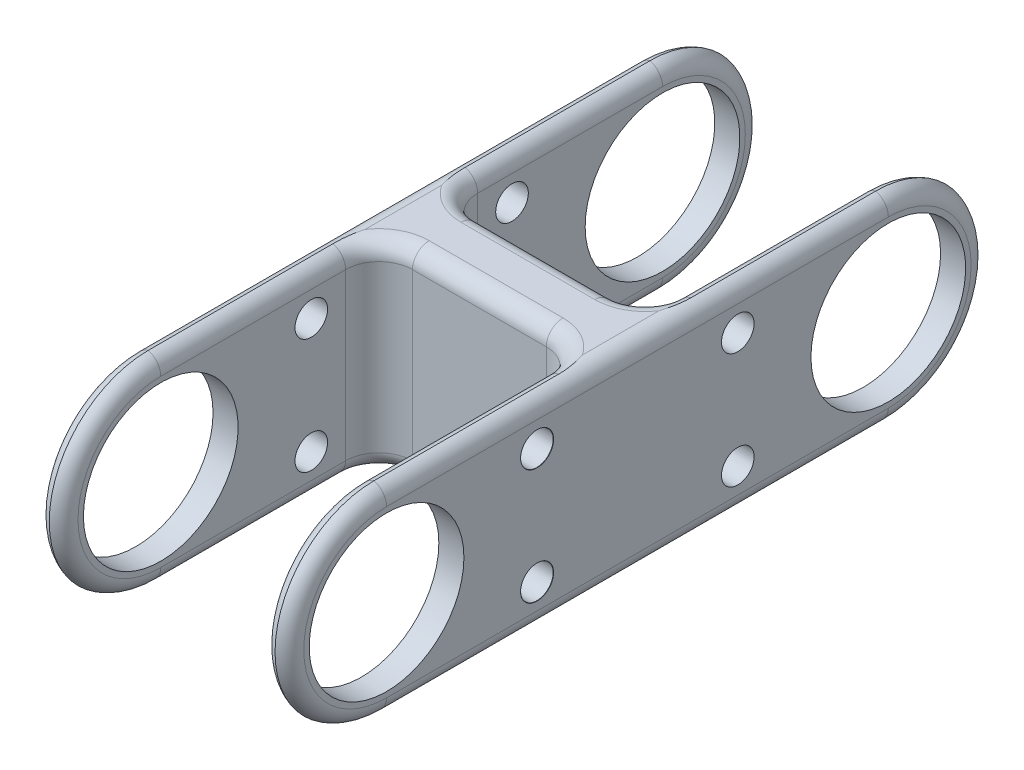
SolidWorks part; units mm, degrees
ref_plane "Front Plane" through (0, 0, 0) normal (0, 0, 1) x (1, 0, 0)
ref_plane "Top Plane" through (0, 0, 0) normal (0, 1, 0) x (1, 0, 0)
ref_plane "Right Plane" through (0, 0, 0) normal (1, 0, 0) x (0, 0, -1)
sketch "Sketch1" plane through (0, 0, 0) normal (1, 0, 0) x (0, 0, -1)
  line L0 (0, 11.9) -> (60, 11.9)
  line L1 (0, -11.9) -> (60, -11.9)
  line L2 (30, 11.9) -> (30, -11.9) construction
  circle A0 centre (0, 0) radius 9.25
  arc A1 (0, 11.9) -> (0, -11.9) centre (0, 0) ccw
  circle A2 centre (60, 0) radius 9.25
  arc A3 (60, 11.9) -> (60, -11.9) centre (60, 0) cw
  dimension "D1" = 18.5
  dimension "D2" = 23.8
  dimension "D3" = 60
extrude "Boss-Extrude1" add sketch "Sketch1" along normal blind 30
sketch "Sketch2" plane through (0, 11.9, 0) normal (0, 1, 0) x (1, 0, 0)
  line L0 (0, -11.9) -> (30, -11.9) construction
  line L1 (3, -11.9) -> (27, -11.9)
  line L2 (3, -11.9) -> (3, 26.1)
  line L3 (3, 26.1) -> (27, 26.1)
  line L4 (27, -11.9) -> (27, 26.1)
  line L5 (0, 30) -> (30, 30) construction
  line L6 (0, 60) -> (0, 0) construction
  line L7 (30, 60) -> (30, 0) construction
  line L8 (3, 33.9) -> (27, 33.9)
  line L9 (27, 71.9) -> (27, 33.9)
  line L10 (3, 71.9) -> (27, 71.9)
  line L11 (3, 71.9) -> (3, 33.9)
  dimension "D1" = 38
  dimension "D2" = 3
  dimension "D3" = 3
extrude "Cut-Extrude1" cut sketch "Sketch2" against normal through all
ref_plane "Plane1" through (0, 0, -30) normal (0, 0, 1) x (1, 0, 0)
fillet "Fillet1" radius 4 4 edges at (27, 0, -26.1) (3, 0, -26.1) (27, 0, -33.9) (3, 0, -33.9)
hole_wizard "M3.5 Clearance Hole1" positions "Sketch3" profile "Sketch4" hole size "M3.5" standard "ANSI Metric" end condition through all
sketch "Sketch3" plane through (0, 0, 0) normal (-1, 0, 0) x (0, 0, 1)
  circle A0 centre (-42, 6.9) radius 1.7024 construction
  point P0 (-42, -6.9)
  point P3 (-42, 6.9)
  point P10 (-41.9779, 15.1169)
  point P11 (-42, 6.9)
sketch "Sketch4" plane through (0, -6.9, -42) normal (0, 1, 0) x (0, 0, 1)
  line L0 (0, 0) -> (0, 30)
  line L1 (0, 30) -> (1.95, 30)
  line L2 (1.95, 30) -> (1.95, 0.025)
  line L3 (1.95, 0.025) -> (1.975, 0)
  line L5 (1.975, 0) -> (0, 0)
  line L6 (-1.95, 0.025) -> (-1.975, 0) construction
  line L11 (0, -6.35) -> (0, 107.95) construction
  dimension "Thru Hole Dia." = 3.9
  dimension "Thru Hole Depth" = 30
  dimension "Near C'Sink Dia." = 3.95
  dimension "Near C'Sink Angle" = 90
sketch "Sketch5" plane through (0, 0, -33.9) normal (0, 0, -1) x (-1, 0, 0)
  line L0 (-23, 11.9) -> (-23, -11.9) construction
  line L1 (-23, 0) -> (-7, 0) construction
  line L2 (-7, -11.9) -> (-7, 11.9) construction
  line B0 (-23, -3.65) -> (-23, -10.15)
  line B1 (-23, -3.65) -> (-20, -3.65)
  line B2 (-20, -3.65) -> (-20, -10.15)
  line B3 (-23, -10.15) -> (-20, -10.15)
  line B4 (-23, 0) -> (-7, 0) construction
  line B5 (-14.9675, -0.1255) -> (-15, -8.8352) construction
  line B6 (-7.01, -10.2096) -> (-10.0099, -10.1872)
  line B7 (-9.9615, -3.6874) -> (-10.0099, -10.1872)
  line B8 (-6.9616, -3.7098) -> (-9.9615, -3.6874)
  line B9 (-6.9616, -3.7098) -> (-7.01, -10.2096)
  line B10 (-6.9616, 3.7098) -> (-7.01, 10.2096)
  line B11 (-6.9616, 3.7098) -> (-9.9615, 3.6874)
  line B12 (-9.9615, 3.6874) -> (-10.0099, 10.1872)
  line B13 (-7.01, 10.2096) -> (-10.0099, 10.1872)
  line B14 (-23, 10.15) -> (-20, 10.15)
  line B15 (-20, 3.65) -> (-20, 10.15)
  line B16 (-23, 3.65) -> (-20, 3.65)
  line B17 (-23, 3.65) -> (-23, 10.15)
sketch_block_instance "Block1-1"
sketch_block "Block1" parameters "D1"=3, "D2"=6.5
sketch "Sketch6" plane through (30, 0, 0) normal (-1, 0, 0) x (0, 0, 1)
  line L0 (-40.025, -6.9) -> (-43.975, -6.9) construction
  circle A0 centre (-42, -6.9) radius 1.975 construction
hole_wizard "M3.5 Clearance Hole2" positions "Sketch9" profile "Sketch8" hole size "M3.5" standard "ANSI Metric" end condition through all
sketch "Sketch9" plane through (30, 0, 0) normal (1, 0, 0) x (0, 0, -1)
  circle A0 centre (18, -6.9) radius 1.975 construction
  circle A1 centre (18, 6.9) radius 1.975 construction
  circle A2 centre (18, -6.9) radius 1.975 construction
  circle A3 centre (18, 6.9) radius 1.975 construction
  point P0 (18, 6.9)
  point P3 (18, -6.9)
sketch "Sketch8" plane through (30, 6.9, -18) normal (0, 1, 0) x (0, 0, -1)
  line L0 (0, 0) -> (0, 30)
  line L1 (0, 30) -> (1.95, 30)
  line L2 (1.95, 30) -> (1.95, 0.025)
  line L3 (1.95, 0.025) -> (1.975, 0)
  line L5 (1.975, 0) -> (0, 0)
  line L6 (-1.95, 0.025) -> (-1.975, 0) construction
  line L11 (0, -6.35) -> (0, 107.95) construction
  dimension "Thru Hole Dia." = 3.9
  dimension "Thru Hole Depth" = 30
  dimension "Near C'Sink Dia." = 3.95
  dimension "Near C'Sink Angle" = 90
sketch "Sketch10" plane through (0, 0, -26.1) normal (0, 0, 1) x (1, 0, 0)
  line L0 (-1.0691, -12.5585) -> (14.9309, -12.5585) construction
  line L1 (23, 0) -> (7, 0) construction
  line L2 (23, -11.9) -> (23, 11.9) construction
  line L3 (7, 11.9) -> (7, -11.9) construction
  line B0 (7, -3.65) -> (7, -10.15)
  line B1 (7, -3.65) -> (10, -3.65)
  line B2 (10, -3.65) -> (10, -10.15)
  line B3 (7, -10.15) -> (10, -10.15)
  line B4 (7, 0) -> (23, 0) construction
  line B5 (15.0325, -0.1255) -> (15, -8.8352) construction
  line B6 (22.99, -10.2096) -> (19.9901, -10.1872)
  line B7 (20.0385, -3.6874) -> (19.9901, -10.1872)
  line B8 (23.0384, -3.7098) -> (20.0385, -3.6874)
  line B9 (23.0384, -3.7098) -> (22.99, -10.2096)
  line B10 (23.0384, 3.7098) -> (22.99, 10.2096)
  line B11 (23.0384, 3.7098) -> (20.0385, 3.6874)
  line B12 (20.0385, 3.6874) -> (19.9901, 10.1872)
  line B13 (22.99, 10.2096) -> (19.9901, 10.1872)
  line B14 (7, 10.15) -> (10, 10.15)
  line B15 (10, 3.65) -> (10, 10.15)
  line B16 (7, 3.65) -> (10, 3.65)
  line B17 (7, 3.65) -> (7, 10.15)
sketch_block_instance "Block1-2"
fillet "Fillet2" [suppressed] radius 2
hole_wizard "M3.5 Clearance Hole3" positions "Sketch11" profile "Sketch12" hole size "M3.5" standard "ANSI Metric" end condition through all
sketch "Sketch11" plane through (30, 0, 0) normal (1, 0, 0) x (0, 0, -1)
  point P0 (18, 6.9)
  point P3 (18, -6.9)
sketch "Sketch12" plane through (30, 6.9, -18) normal (0, 1, 0) x (0, 0, -1)
  line L0 (0, 0) -> (0, 30)
  line L1 (0, 30) -> (1.95, 30)
  line L2 (1.95, 30) -> (1.95, 0.025)
  line L3 (1.95, 0.025) -> (1.975, 0)
  line L5 (1.975, 0) -> (0, 0)
  line L6 (-1.95, 0.025) -> (-1.975, 0) construction
  line L11 (0, -6.35) -> (0, 107.95) construction
  dimension "Thru Hole Dia." = 3.9
  dimension "Thru Hole Depth" = 30
  dimension "Near C'Sink Dia." = 3.95
  dimension "Near C'Sink Angle" = 90
sketch "Sketch13" [suppressed] plane through (0, 0, 0) normal (-1, 0, 0) x (0, 0, 1)
  line L0 (-125.6084, 9.9) -> (-125.6084, -9.9) construction
  line L1 (0, 9.9) -> (-60, 9.9) construction
  line L2 (-60, -9.9) -> (0, -9.9) construction
  point P0 (-128.6084, 6.9)
  dimension "D1" = 3
fillet "Fillet3" radius 2 32 edges at (0, 0, -71.9) (0, -11.9, -30) (0, 0, 11.9) (3, 0, -71.9) (3, -11.9, -48.95) (4.1716, -11.9, -35.0716) (15, -11.9, -33.9) (25.8284, -11.9, -35.0716) (27, -11.9, -48.95) (27, 0, -71.9) (30, 0, -71.9) (30, -11.9, -30) (30, 0, 11.9) (27, 0, 11.9) (27, -11.9, -11.05) (25.8284, -11.9, -24.9284) (15, -11.9, -26.1) (4.1716, -11.9, -24.9284) (3, -11.9, -11.05) (3, 0, 11.9) (0, 11.9, -30) (3, 11.9, -48.95) (4.1716, 11.9, -35.0716) (15, 11.9, -33.9) (25.8284, 11.9, -35.0716) (27, 11.9, -48.95) (30, 11.9, -30) (27, 11.9, -11.05) (25.8284, 11.9, -24.9284) (15, 11.9, -26.1) (4.1716, 11.9, -24.9284) (3, 11.9, -11.05)
